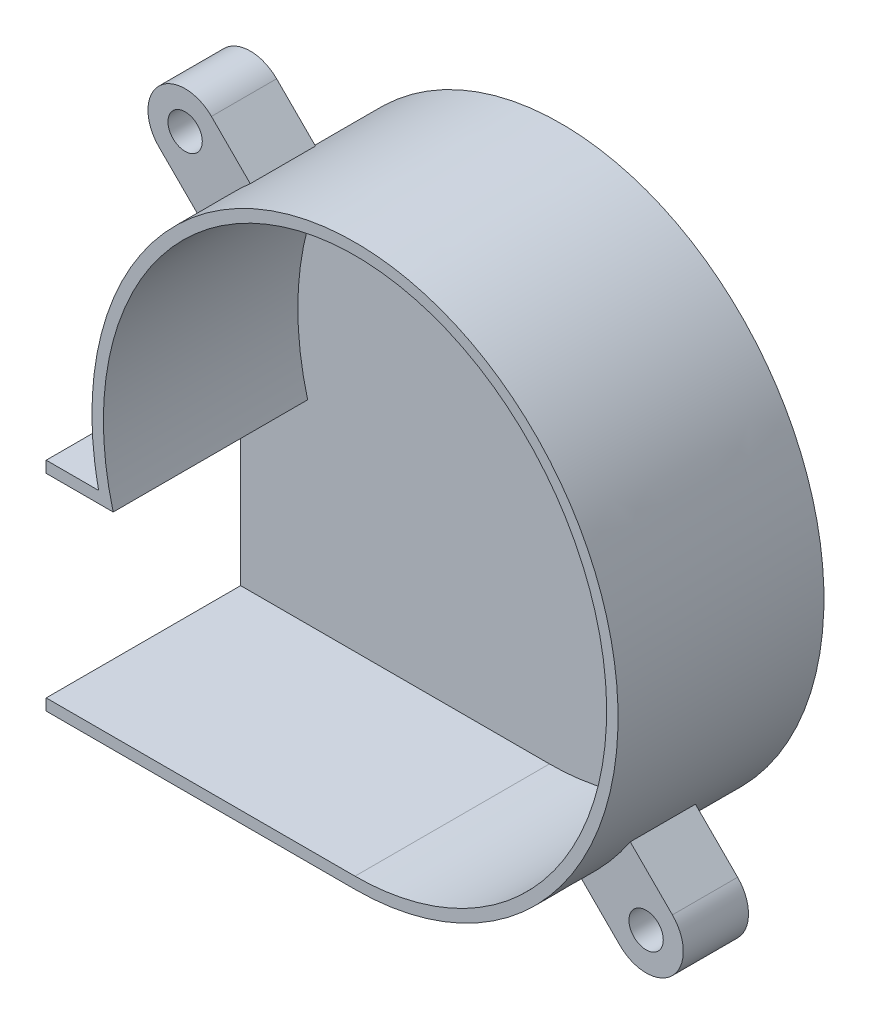
SolidWorks part; units mm, degrees
ref_plane "Plano frontal" through (0, 0, 0) normal (0, 0, 1) x (1, 0, 0)
ref_plane "Plano superior" through (0, 0, 0) normal (0, 1, 0) x (1, 0, 0)
ref_plane "Plano direito" through (0, 0, 0) normal (1, 0, 0) x (0, 0, -1)
sketch "Esboço1" plane through (0, 0, 0) normal (0, 0, 1) x (1, 0, 0)
  line L0 (0, -24.5) -> (-27, -24.5)
  line L1 (-27, -24.5) -> (-27, -5.5)
  line L2 (-27, -5.5) -> (-22.413, -5.5)
  line L3 (0, -23.5) -> (-26, -23.5)
  line L4 (-26, -23.5) -> (-26, -6.5)
  line L5 (-26, -6.5) -> (-21.1416, -6.5)
  line L6 (-26, -6.5) -> (-27, -6.5)
  line L8 (-27, -23.5) -> (-26, -23.5)
  ellipse E0 centre (0, 0) end of major axis (0, 24.5) minor radius 23 (0, -24.5) -> (-22.413, -5.5) ccw
  spline S0 degree 1 poles (0, -23.5) (-21.1416, -6.5) knots 0 0 1 1 construction
  spline S1 degree 3 poles (-21.1416, -6.5) (-21.7759, -4.1462) (-22.35, 0.7769) (-21.0411, 8.0855) (-17.6937, 14.6033) (-12.642, 19.6989) (-6.3826, 22.8884) (0.482, 23.8764) (7.3009, 22.5731) (13.4272, 19.0971) (18.2691, 13.7715) (21.3496, 7.1038) (22.3606, -0.259) (21.2003, -7.5965) (17.9858, -14.1907) (13.037, -19.4026) (6.8455, -22.7361) (2.2763, -23.5) (0, -23.5) knots -3.141593 -3.141593 -3.141593 -3.141593 -2.829596 -2.5176 -2.205603 -1.893607 -1.58161 -1.269614 -0.957618 -0.645621 -0.333625 -0.021628 0.290368 0.602365 0.914361 1.226357 1.538354 1.85035 1.85035 1.85035 1.85035
  point P16 (-27, -23.5)
  point P17 (-27, -23.5)
  dimension "D1" = 49
  dimension "D5" = 1
  dimension "D2" = 46
  dimension "D3" = 50
  dimension "D4" = 19
extrude "Ressalto-extrusão1" add sketch "Esboço1" along normal blind 1 contours E0 L2 L1 L0
extrude "Ressalto-extrusão2" add sketch "Esboço1<3>" along normal blind 18 contours L5 S1 L3 L8 L1 L0 E0 L2 L6 region at (-13.5, -23.7999, 0)
sketch "Esboço1<3>" plane through (0, 0, 0) normal (0, 0, 1) x (1, 0, 0) same geometry as "Esboço1"
sketch "Esboço2" plane through (0, 0, 0) normal (0, 0, 1) x (1, 0, 0)
  line L0 (-20.1525, 20.1525) -> (20.1525, -20.1525) construction
  line L1 (-27, -23.5) -> (0, -23.5) construction
  line L2 (22.4506, -17.8544) -> (18.7642, -14.168)
  line L3 (-14.458, 19.0542) -> (-17.8544, 22.4506)
  line L4 (17.8544, -22.4506) -> (14.458, -19.0542)
  line L5 (-18.7642, 14.168) -> (-22.4506, 17.8544)
  arc A0 (-17.8544, 22.4506) -> (-22.4506, 17.8544) centre (-20.1525, 20.1525) ccw
  arc A1 (17.8544, -22.4506) -> (22.4506, -17.8544) centre (20.1525, -20.1525) ccw
  circle A2 centre (20.1525, -20.1525) radius 1.5
  circle A3 centre (-20.1525, 20.1525) radius 1.5
  ellipse E0 centre (0, 0) end of major axis (0, 24.5) minor radius 23 (0, -24.5) -> (-22.413, -5.5) ccw construction
  ellipse E1 centre (0, 0) end of major axis (0, 24.5) minor radius 23 (14.458, -19.0542) -> (18.7642, -14.168) ccw
  ellipse E2 centre (0, 0) end of major axis (0, 24.5) minor radius 23 (-14.458, 19.0542) -> (-18.7642, 14.168) ccw
  point P6 (0, 0)
  dimension "D3" = 3
  dimension "D4" = 6.5
  dimension "D1" = 57
  dimension "D2" = 45
extrude "Ressalto-extrusão3" add sketch "Esboço2" along normal blind 5.7 from offset 7
